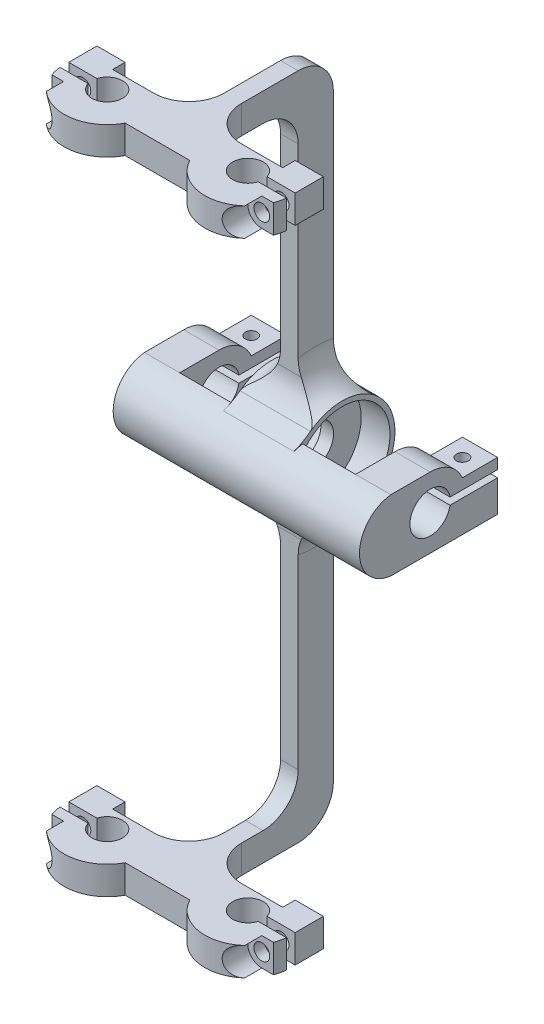
SolidWorks part; units mm, degrees
material "PLA Black"
ref_plane "Front" through (0, 0, 0) normal (0, 0, 1) x (1, 0, 0)
ref_plane "Top" through (0, 0, 0) normal (0, 1, 0) x (1, 0, 0)
ref_plane "Right" through (0, 0, 0) normal (1, 0, 0) x (0, 0, -1)
sketch "Sketch1" plane through (0, 0, 0) normal (1, 0, 0) x (0, 0, -1)
  line L0 (7.328, 87) -> (7.328, -87) construction
  line L1 (-11.4058, 95) -> (-11.4058, 87)
  line L2 (-11.4058, 87) -> (26.0619, 87)
  line L3 (-11.4058, 95) -> (36.0619, 95)
  line L4 (-19.0433, 0) -> (30.354, 0) construction
  line L5 (-11.4058, -95) -> (36.0619, -95)
  line L6 (-11.4058, -87) -> (26.0619, -87)
  line L7 (-11.4058, -95) -> (-11.4058, -87)
  line L8 (36.0619, 95) -> (36.0619, -5.7556)
  line L9 (26.0619, 87) -> (26.0619, -87)
  line L10 (36.0619, -5.7556) -> (36.0619, -95)
  dimension "D1" = 190
  dimension "D2" = 8
  dimension "D3" = 10
extrude "Boss-Extrude1" add sketch "Sketch1" along normal mid plane 5
sketch "Sketch2" plane through (0, 95, -93.2787) normal (0, -1, 0) x (1, 0, 0)
  line L0 (-24.1665, 93.2787) -> (24.1665, 93.2787)
  line L1 (24.1665, 93.2787) -> (24.1665, 89.7316)
  line L2 (24.1665, 89.7316) -> (32.1665, 89.7316)
  line L3 (24.1665, 97.7316) -> (24.1665, 85.5924) construction
  line L4 (32.1665, 89.7316) -> (32.1665, 97.7316)
  line L5 (0, 80.7776) -> (0, 113.4638) construction
  line L6 (-9.1804, 104.6846) -> (9.1804, 104.6846)
  line L7 (32.1665, 97.7316) -> (24.1665, 97.7316)
  line L8 (24.1665, 100.2316) -> (32.1665, 100.2316)
  line L9 (-24.1665, 100.2316) -> (-32.1665, 100.2316)
  line L10 (-32.1665, 97.7316) -> (-24.1665, 97.7316)
  line L11 (-24.1665, 89.7316) -> (-32.1665, 89.7316)
  line L12 (-32.1665, 89.7316) -> (-32.1665, 97.7316)
  line L13 (-24.1665, 89.7316) -> (-24.1665, 93.2787)
  line L14 (-2.5, 104.6846) -> (21.1341, 104.6846) construction
  line L15 (20, 104.6846) -> (20, 93.2787) construction
  arc A0 (32.1665, 100.2316) -> (9.1804, 104.6846) centre (20, 98.9816) ccw
  arc A1 (-32.1665, 100.2316) -> (-9.1804, 104.6846) centre (-20, 98.9816) cw
  arc A2 (24.1665, 100.2316) -> (24.1665, 97.7316) centre (20, 98.9816) ccw
  arc A3 (-24.1665, 100.2316) -> (-24.1665, 97.7316) centre (-20, 98.9816) cw
  arc A4 (-24.1665, 100.2316) -> (-24.1665, 97.7316) centre (-20, 98.9816) cw
  line M5 (-2.5, 57.2168) -> (-2.5, 104.6846)
  line M7 (2.5, 104.6846) -> (2.5, 57.2168)
  dimension "D2" = 2.5
  dimension "D3" = 8.7
  dimension "D4" = 8
  dimension "D1" = 40
  dimension "D5" = 8
extrude "Boss-Extrude2" add sketch "Sketch2" along normal blind 8 contours A3 L9 A1 L6 L0 L13 L11 L12 L10 M5 | L8 A2 L7 L4 L2 L1 L0 L6 A0 M7 region at (-24.5328, 95, -1.7735) region at (2.8663, 95, 5.7029)
sketch "Sketch7" plane through (0, 0, -3.5471) normal (0, 0, -1) x (-1, 0, 0)
  line L0 (-28.1665, 95) -> (-28.1665, 87) construction
  line L1 (-24.1665, 95) -> (-32.1665, 95) construction
  line L3 (-32.1665, 91) -> (-24.1665, 91) construction
  line L4 (-32.1665, 87) -> (-32.1665, 95) construction
  line L5 (-24.1665, 87) -> (-24.1665, 95) construction
  line L6 (0, 111.5451) -> (0, 86.699) construction
  line L7 (-24.1665, 87) -> (-32.1665, 87) construction
  circle A0 centre (-28.1665, 91) radius 2.25
  circle A1 centre (28.1665, 91) radius 2.25
  dimension "D1" = 4.5
extrude "Cut-Extrude3" cut sketch "Sketch7" against normal through all
ref_plane "Plane1" through (0, 0, 17.9335) normal (0, 0, 1) x (1, 0, 0)
sketch "Sketch8" plane through (0, 0, 17.9335) normal (0, 0, 1) x (1, 0, 0)
  line L1 (0, 111.4996) -> (0, 91.8899) construction
  line L2 (28.1665, 95) -> (32.1665, 95)
  line L3 (32.1665, 95) -> (32.1665, 87)
  line L4 (32.1665, 87) -> (28.1665, 87)
  line L5 (24.1665, 95) -> (32.1665, 95) construction
  line L6 (-32.1665, 87) -> (-28.1665, 87)
  line L7 (-32.1665, 95) -> (-32.1665, 87)
  line L8 (-28.1665, 95) -> (-32.1665, 95)
  arc A0 (28.1665, 95) -> (28.1665, 87) centre (28.1665, 91) ccw
  arc A1 (-28.1665, 95) -> (-28.1665, 87) centre (-28.1665, 91) cw
extrude "Cut-Extrude4" cut sketch "Sketch8" against normal blind 8
mirror "Mirror4" about plane through (0, 0, 0) normal (0, 1, 0) of "Boss-Extrude2", "Cut-Extrude3", "Cut-Extrude4"
sketch "Sketch4" plane through (0, 0, 0) normal (1, 0, 0) x (0, 0, -1)
  line L0 (31.0619, 6.4033) -> (31.0619, -4.3005) construction
  line L2 (26.0619, 87) -> (26.0619, -87) construction
  line L3 (36.0619, -95) -> (36.0619, 95) construction
  circle A0 centre (31.0619, 0) radius 15
  dimension "D1" = 30
extrude "Boss-Extrude4" add sketch "Sketch4" along normal mid plane 20 contours A0
sketch "Sketch5" plane through (10, 0, 0) normal (1, 0, 0) x (0, 0, -1)
  circle A0 centre (31.0619, 0) radius 13.6
  circle A1 centre (31.0619, 0) radius 15 construction
  dimension "D1" = 27.2
extrude "Cut-Extrude1" cut sketch "Sketch5" against normal blind 8.2
mirror "Mirror3" about plane through (0, 0, 0) normal (1, 0, 0) of "Cut-Extrude1"
sketch "Sketch6" plane through (1.8, 0, 0) normal (1, 0, 0) x (0, 0, -1)
  circle A0 centre (31.0619, 0) radius 5.75
  circle A1 centre (31.0619, 0) radius 13.6 construction
  dimension "D1" = 11.5
extrude "Cut-Extrude2" cut sketch "Sketch6" against normal through all contours A0
fillet "Fillet1" radius 10 16 edges at (0, -87, -26.0619) (0, 87, -26.0619) (2.5, -15, -31.0619) (0, -14.1421, -36.0619) (-2.5, -15, -31.0619) (0, -14.1421, -26.0619) (0, 14.1421, -26.0619) (-2.5, 15, -31.0619) (0, 14.1421, -36.0619) (2.5, 15, -31.0619) (2.5, -91, 0) (-2.5, -91, 0) (0, -95, -36.0619) (0, 95, -36.0619)
sketch "Sketch9" plane through (0, 0, 0) normal (1, 0, 0) x (0, 0, -1)
  arc A0 (19.8816, 10) -> (19.8816, -10) centre (31.0619, 0) ccw
  arc A1 (22.0619, 12) -> (22.0619, -12) centre (31.0619, 0) ccw construction
  arc A2 (19.8816, 10) -> (19.8816, -10) centre (21.0619, 0) ccw
  dimension "D2" = 10
  dimension "D1" = 20
extrude "Boss-Extrude5" add sketch "Sketch9" along normal mid plane 70
sketch "Sketch10" plane through (35, 0, 0) normal (1, 0, 0) x (0, 0, -1)
  line L0 (45.2271, 6.4781) -> (45.2271, -13.1071) construction
  line L1 (19.8816, -10) -> (50.2271, -10)
  line L2 (50.2271, -10) -> (50.2271, -1)
  line L3 (50.2271, -1) -> (36.7243, -1)
  line L4 (36.7243, 1) -> (50.2271, 1)
  line L5 (50.2271, 1) -> (50.2271, 4)
  line L6 (50.2271, 4) -> (40.2271, 4)
  line L7 (31.0619, 10) -> (19.8816, 10)
  line L8 (31.0619, 0) -> (57.7194, 0) construction
  circle A0 centre (31.0619, 0) radius 5.75 construction
  arc A1 (36.7243, -1) -> (36.7243, 1) centre (31.0619, 0) cw
  arc A2 (40.2271, 4) -> (31.0619, 10) centre (31.0619, 0) ccw
  arc A4 (19.8816, 10) -> (19.8816, -10) centre (31.0619, 0) ccw construction
  arc A5 (19.8816, 10) -> (19.8816, -10) centre (31.0619, 0) ccw
  dimension "D1" = 10
  dimension "D2" = 3
  dimension "D3" = 2
extrude "Boss-Extrude6" add sketch "Sketch10" against normal blind 10
hole_wizard "M3 Clearance Hole1" positions "Sketch12" profile "Sketch11" hole size "M3" standard "DIN" end condition up to next
sketch "Sketch12" plane through (0, 4, 0) normal (0, 1, 0) x (1, 0, 0)
  line L4 (35, 45.2271) -> (25, 45.2271) construction
  line L5 (35, 50.2271) -> (35, 40.2271) construction
  line L6 (25, 50.2271) -> (25, 40.2271) construction
  point P0 (30, 45.2271)
sketch "Sketch11" plane through (30, 4, -45.2271) normal (1, 0, 0) x (0, 0, 1)
  line L0 (0, 0) -> (0, 3.001)
  line L1 (0, 3.001) -> (1.7, 3.001)
  line L2 (1.7, 3.001) -> (1.7, 0)
  line L5 (1.7, 0) -> (0, 0)
  line L11 (0, -6.35) -> (0, 107.95) construction
  dimension "Thru Hole Dia." = 3.4
  dimension "Thru Hole Depth" = 3.001
sketch "Sketch14" plane through (0, -10, 0) normal (0, -1, 0) x (1, 0, 0)
  circle A0 centre (30, -45.2271) radius 2.325
  circle A2 centre (30, -45.2271) radius 1.7 construction
  dimension "D1" = 4.65
extrude "Cut-Extrude5" cut sketch "Sketch14" against normal up to next
mirror "Mirror5" about plane through (0, 0, 0) normal (1, 0, 0) of "Cut-Extrude5", "M3 Clearance Hole1", "Boss-Extrude6"
fillet "Fillet3" radius 20 2 edges at (0, -10, -19.8816) (0, 10, -19.8816)
